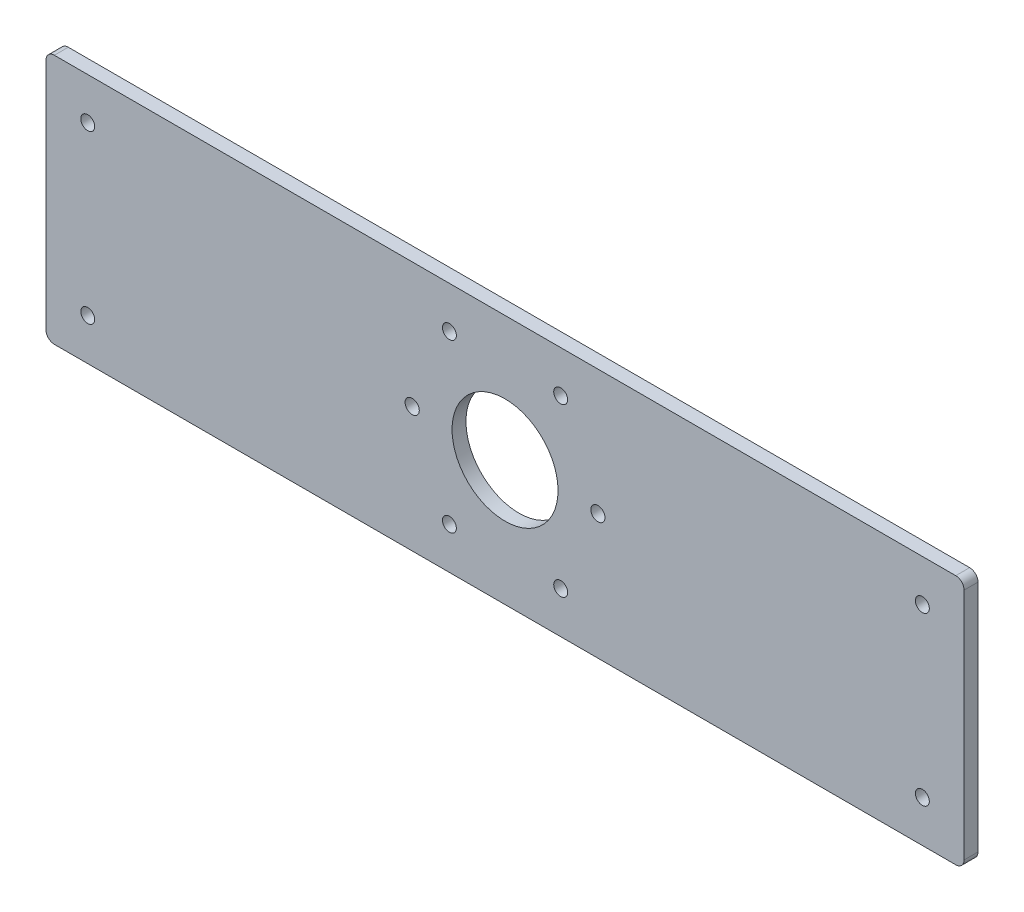
SolidWorks part; units mm, degrees
ref_plane "Front Plane" through (0, 0, 0) normal (0, 0, 1) x (1, 0, 0)
ref_plane "Top Plane" through (0, 0, 0) normal (0, 1, 0) x (1, 0, 0)
ref_plane "Right Plane" through (0, 0, 0) normal (1, 0, 0) x (0, 0, -1)
sketch "Sketch1" plane through (0, 0, 0) normal (0, 0, 1) x (1, 0, 0)
  line L0 (-165, 0) -> (165, 0) construction
  line L1 (165, -45) -> (-165, -45)
  line L2 (165, -45) -> (165, 45)
  line L3 (165, 45) -> (-165, 45)
  line L4 (-165, -45) -> (-165, 45)
  line L5 (165, -45) -> (-165, 45) construction
  line L6 (165, 45) -> (-165, -45) construction
  line L8 (0, -33.3754) -> (33.3754, 0) construction
  line L9 (0, -33.3754) -> (-33.3754, 0) construction
  line L10 (-33.3754, 0) -> (0, 33.3754) construction
  line L11 (33.3754, 0) -> (0, 33.3754) construction
  line L12 (0, -33.3754) -> (0, 33.3754) construction
  line L13 (-33.3754, 0) -> (33.3754, 0) construction
  circle A0 centre (0, 0) radius 19.05
  circle A1 centre (-33.3754, 0) radius 2.55
  circle A2 centre (33.3754, 0) radius 2.55
  point P0 (0, 0)
  dimension "D3" = 38.1
  dimension "D4" = 47.2
  dimension "D5" = 47.2
  dimension "D8" = 5.1
  dimension "D9" = 5.1
  dimension "D1" = 90
  dimension "D2" = 330
  dimension "D6" = 90
  dimension "D7" = 90
extrude "Boss-Extrude1" add sketch "Sketch1" along normal mid plane 5
sketch "Sketch2" plane through (0, 0, 2.5) normal (0, 0, 1) x (1, 0, 0)
  line L2 (-150, 45) -> (-150, -45)
  line L3 (-150, 45) -> (-150, -45) construction
  line L5 (150, -45) -> (150, 45)
  line L6 (150, -45) -> (150, 45) construction
  line L23 (165, 30) -> (-165, 30)
  line L24 (165, 30) -> (-165, 30) construction
  line L25 (0, 45) -> (0, -45) construction
  line L26 (-165, -30) -> (165, -30)
  line L27 (-165, -30) -> (165, -30) construction
  line L28 (165, 45) -> (-165, 45) construction
  line L29 (-165, -45) -> (165, -45) construction
  line L30 (-20, 45) -> (-20, -45) construction
  line L31 (20, 45) -> (20, -45) construction
  circle A0 centre (-150, 30) radius 2.5
  circle A1 centre (-150, -30) radius 2.5
  circle A2 centre (-20, 30) radius 2.5
  circle A3 centre (-20, -30) radius 2.5
  circle A4 centre (20, -30) radius 2.5
  circle A5 centre (20, 30) radius 2.5
  circle A6 centre (150, 30) radius 2.5
  circle A7 centre (150, -30) radius 2.5
  dimension "D7" = 5
  dimension "D8" = 5
  dimension "D9" = 5
  dimension "D10" = 5
  dimension "D11" = 5
  dimension "D12" = 5
  dimension "D13" = 5
  dimension "D14" = 5
  dimension "D1" = 15
  dimension "D2" = 15
  dimension "D3" = 15
  dimension "D4" = 15
  dimension "D5" = 20
  dimension "D6" = 20
extrude "Cut-Extrude1" cut sketch "Sketch2" against normal through all
fillet "Fillet1" radius 3 4 edges at (-165, -45, 0) (165, -45, 0) (165, 45, 0) (-165, 45, 0)
